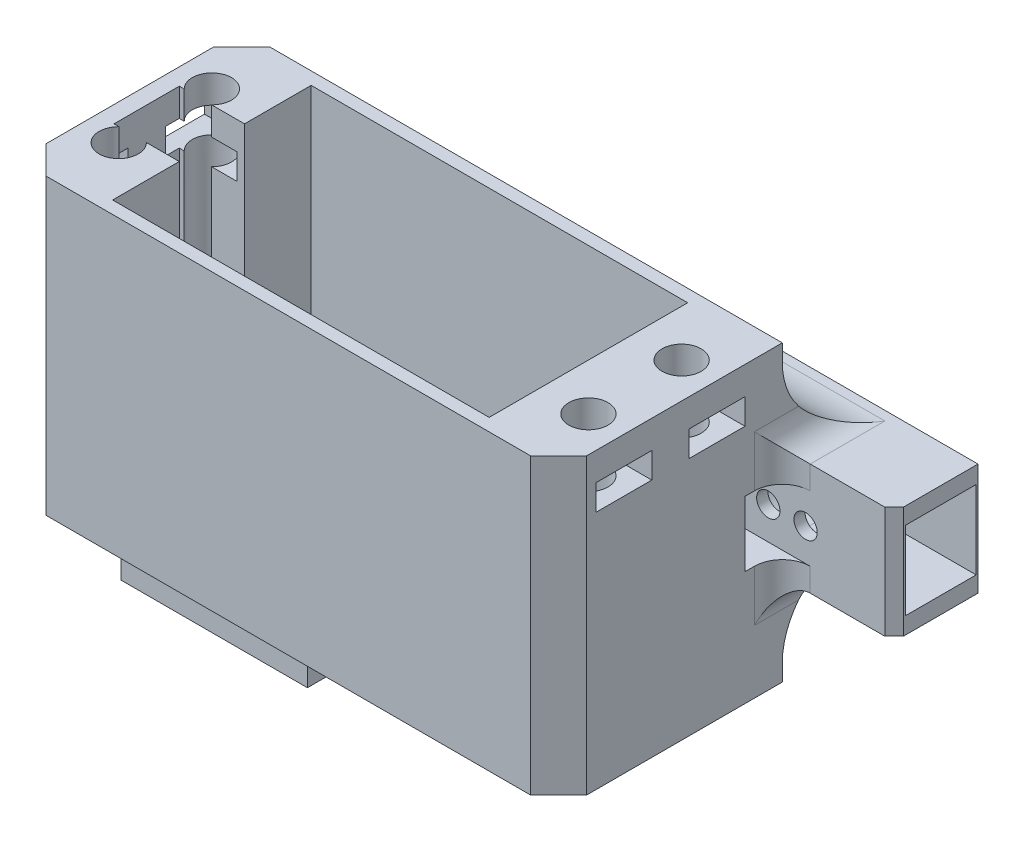
SolidWorks part; units mm, degrees
ref_plane "Front Plane" through (0, 0, 0) normal (0, 0, 1) x (1, 0, 0)
ref_plane "Top Plane" through (0, 0, 0) normal (0, 1, 0) x (1, 0, 0)
ref_plane "Right Plane" through (0, 0, 0) normal (1, 0, 0) x (0, 0, -1)
sketch "Sketch1" plane through (0, 0, 0) normal (0, 1, 0) x (1, 0, 0)
  line L0 (9.75, 1.0273) -> (50.15, 1.0273)
  line L1 (50.15, 1.0273) -> (50.15, -20.2727)
  line L2 (50.15, -20.2727) -> (9.75, -20.2727)
  line L4 (0.95, -21.6227) -> (58.95, -21.6227)
  line L5 (58.95, -21.6227) -> (58.95, 2.3773)
  line L6 (58.95, 2.3773) -> (0.95, 2.3773)
  line L8 (55.15, -4.6227) -> (55.15, -14.6227) construction
  line L9 (0.95, 2.3773) -> (0.95, -21.6227)
  line L10 (9.75, 1.0273) -> (9.75, -20.2727)
  line L11 (29.95, 1.0273) -> (29.95, -20.2727) construction
  circle A0 centre (55.15, -4.6227) radius 2.1
  circle A1 centre (55.15, -14.6227) radius 2.1
  circle A2 centre (4.75, -14.6227) radius 2.1
  circle A3 centre (4.75, -4.6227) radius 2.1
  point P13 (55.15, -9.6227)
  point P14 (50.15, -9.6227)
  point P20 (0.95, -9.6227)
  point P22 (29.95, 2.3773)
  dimension "D1" = 4.2
  dimension "D2" = 10
  dimension "D3" = 24
  dimension "D4" = 40.4
  dimension "D5" = 5
  dimension "D6" = 21.3
  dimension "D7" = 58
extrude "Boss-Extrude1" add sketch "Sketch1" along normal blind 28.35
sketch "Sketch11" plane through (0, 0, 0) normal (0, -1, 0) x (1, 0, 0)
  line L1 (0.95, 21.6227) -> (58.95, 21.6227)
  line L2 (0.95, 21.6227) -> (0.95, -2.3773)
  line L3 (0.95, -2.3773) -> (58.95, -2.3773)
  line L4 (58.95, 21.6227) -> (58.95, -2.3773)
extrude "Boss-Extrude5" add sketch "Sketch11" along normal blind 3.175
sketch "Sketch14" plane through (0, 0, -2.3773) normal (0, 0, -1) x (-1, 0, 0)
  line L7 (-58.95, 28.35) -> (-58.95, -3.175) construction
  line L8 (-46.95, 6.5875) -> (-70.95, 6.5875)
  line L9 (-46.95, 6.5875) -> (-46.95, 18.5875)
  line L10 (-46.95, 18.5875) -> (-70.95, 18.5875)
  line L11 (-70.95, 6.5875) -> (-70.95, 18.5875)
  line L12 (-46.95, 6.5875) -> (-70.95, 18.5875) construction
  line L13 (-46.95, 18.5875) -> (-70.95, 6.5875) construction
  point P0 (-58.95, 12.5875)
  point P5 (-58.95, 12.5875)
  dimension "D1" = 24
  dimension "D2" = 12
  dimension "D3" = 0
extrude "Boss-Extrude7" add sketch "Sketch14" along normal blind 10
ref_plane "Plane1" through (0, 0, -7.3773) normal (0, 0, 1) x (1, 0, 0)
sketch "Sketch16" plane through (0, 0, -7.3773) normal (0, 0, 1) x (1, 0, 0)
  line L0 (70.95, 18.5875) -> (70.95, 6.5875) construction
  line L1 (57.45, 8.3875) -> (70.95, 8.3875)
  line L3 (57.45, 16.7875) -> (70.95, 16.7875)
  line L4 (70.95, 8.3875) -> (70.95, 16.7875)
  line L5 (46.95, 6.5875) -> (46.95, 18.5875) construction
  arc A0 (57.45, 16.7875) -> (57.45, 8.3875) centre (57.45, 12.5875) ccw
  point P9 (46.95, 12.5875)
  point P10 (70.95, 12.5875)
  dimension "D2" = 4.2
  dimension "D1" = 13.5
extrude "Cut-Extrude1" cut sketch "Sketch16" against normal mid plane 7.6
sketch "Sketch18" plane through (0, 0, -12.3773) normal (0, 0, -1) x (-1, 0, 0)
  arc A0 (-60.2, 12.5875) -> (-62.7, 12.5875) centre (-61.45, 12.5875) ccw construction
  arc A1 (-62.7, 12.5875) -> (-60.2, 12.5875) centre (-61.45, 12.5875) ccw construction
  arc A2 (-56.2, 12.5875) -> (-58.7, 12.5875) centre (-57.45, 12.5875) ccw construction
  arc A3 (-58.7, 12.5875) -> (-56.2, 12.5875) centre (-57.45, 12.5875) ccw construction
  arc A4 (-60.2, 12.5875) -> (-62.7, 12.5875) centre (-61.45, 12.5875) ccw
  arc A5 (-62.7, 12.5875) -> (-60.2, 12.5875) centre (-61.45, 12.5875) ccw
  arc A6 (-56.2, 12.5875) -> (-58.7, 12.5875) centre (-57.45, 12.5875) ccw
  arc A7 (-58.7, 12.5875) -> (-56.2, 12.5875) centre (-57.45, 12.5875) ccw
extrude "Cut-Extrude2" cut sketch "Sketch18" against normal up to surface (10 mm away) up to face at (64.95, 12.5875, -2.3773)
fillet "Fillet1" radius 8 3 edges at (52.95, 6.5875, -2.3773) (46.95, 12.5875, -2.3773) (52.95, 18.5875, -2.3773)
chamfer "Chamfer2" distance 3 angle 45 3 edges at (0.95, 12.5875, -2.3773) (0.95, 12.5875, 21.6227) (58.95, 12.5875, 21.6227)
fillet "Fillet2" radius 3 2 edges at (58.95, 6.5875, -6.3773) (58.95, 18.5875, -6.3773)
fillet "Fillet3" radius 3 1 edges at (58.95, 12.5875, -2.3773)
chamfer "Chamfer3" distance 1 angle 45 5 edges at (70.95, 12.5875, -2.3773) (70.95, 12.5875, -12.3773) (58.95, 6.5875, -12.3773) (46.95, 12.5875, -12.3773) (58.95, 18.5875, -12.3773)
ref_plane "Plane2" through (0, 25.35, 0) normal (0, 1, 0) x (1, 0, 0)
sketch "Sketch19" plane through (0, 25.35, 0) normal (0, 1, 0) x (1, 0, 0)
  line L0 (0.95, -0.6227) -> (0.95, -18.6227) construction
  line L1 (0.95, -1.6227) -> (8.95, -1.6227)
  line L2 (0.95, -1.6227) -> (0.95, -7.6227)
  line L3 (0.95, -7.6227) -> (8.95, -7.6227)
  line L4 (8.95, -1.6227) -> (8.95, -7.6227)
  line L5 (-0.5892, -9.6227) -> (60.8708, -9.6227) construction
  line L6 (29.95, -22.0073) -> (29.95, 3.0189) construction
  line L7 (9.75, 1.0273) -> (9.75, -20.2727) construction
  line L8 (50.15, 1.0273) -> (9.75, 1.0273) construction
  line L9 (8.95, -17.6227) -> (8.95, -11.6227)
  line L10 (0.95, -11.6227) -> (8.95, -11.6227)
  line L11 (0.95, -17.6227) -> (0.95, -11.6227)
  line L12 (0.95, -17.6227) -> (8.95, -17.6227)
  line L37 (60.4892, -9.6227) -> (-0.9708, -9.6227) construction
  line L38 (58.95, -17.6227) -> (50.95, -17.6227)
  line L39 (58.95, -17.6227) -> (58.95, -11.6227)
  line L40 (58.95, -11.6227) -> (50.95, -11.6227)
  line L41 (50.95, -17.6227) -> (50.95, -11.6227)
  line L42 (50.95, -1.6227) -> (50.95, -7.6227)
  line L43 (58.95, -7.6227) -> (50.95, -7.6227)
  line L44 (58.95, -1.6227) -> (58.95, -7.6227)
  line L45 (58.95, -1.6227) -> (50.95, -1.6227)
  circle A0 centre (4.75, -4.6227) radius 2.1 construction
  circle A1 centre (4.75, -4.6227) radius 2.1 construction
  circle A2 centre (4.75, -14.6227) radius 2.1 construction
  circle A3 centre (4.75, -4.6227) radius 2.1 construction
  circle A4 centre (4.75, -14.6227) radius 2.1 construction
  circle A5 centre (4.75, -4.6227) radius 2.1 construction
  circle A6 centre (4.75, -14.6227) radius 2.1 construction
  circle A7 centre (4.75, -4.6227) radius 2.1 construction
  circle A8 centre (4.75, -14.6227) radius 2.1 construction
  circle A9 centre (55.15, -14.6227) radius 2.1 construction
  circle A10 centre (55.15, -4.6227) radius 2.1 construction
  circle A11 centre (55.15, -14.6227) radius 2.1 construction
  circle A12 centre (55.15, -4.6227) radius 2.1 construction
  circle A13 centre (55.15, -14.6227) radius 2.1 construction
  circle A14 centre (55.15, -4.6227) radius 2.1 construction
  circle A15 centre (55.15, -14.6227) radius 2.1 construction
  circle A16 centre (55.15, -4.6227) radius 2.1 construction
  point P11 (0.95, -4.6227)
  point P18 (9.75, -9.6227)
  point P21 (29.95, 1.0273)
  point P28 (0.95, -14.6227)
  point P55 (58.95, -14.6227)
  point P56 (58.95, -4.6227)
  dimension "D1" = 6
  dimension "D2" = 8
extrude "Cut-Extrude3" cut sketch "Sketch19" against normal blind 2.75
sketch "Sketch20" plane through (0, 0, 0) normal (0, 1, 0) x (1, 0, 0)
  line L0 (0.95, -0.6227) -> (0.95, -18.6227) construction
  line L1 (0.95, -13.8727) -> (9.75, -13.8727)
  line L2 (0.95, -13.8727) -> (0.95, -5.3727)
  line L3 (0.95, -5.3727) -> (9.75, -5.3727)
  line L4 (9.75, -13.8727) -> (9.75, -5.3727)
  line L5 (9.75, 1.0273) -> (9.75, -20.2727) construction
  point P6 (0.95, -9.6227)
  dimension "D1" = 8.5
extrude "Cut-Extrude4" cut sketch "Sketch20" along normal blind 4
sketch "Sketch21" plane through (0, -3.175, 0) normal (0, -1, 0) x (1, 0, 0)
  line L0 (0.95, 18.6227) -> (0.95, 0.6227) construction
  line L1 (30, -0.3773) -> (10, -0.3773)
  line L2 (30, -0.3773) -> (30, 19.6227)
  line L3 (30, 19.6227) -> (10, 19.6227)
  line L4 (10, -0.3773) -> (10, 19.6227)
  line L5 (30, -0.3773) -> (10, 19.6227) construction
  line L6 (30, 19.6227) -> (10, -0.3773) construction
  point P0 (20, 9.6227)
  point P7 (0.95, 9.6227)
  dimension "D1" = 19.05
  dimension "D2" = 20
  dimension "D3" = 20
extrude "Boss-Extrude8" add sketch "Sketch21" along normal blind 6
sketch "Sketch13" plane through (0, -9.175, 0) normal (0, -1, 0) x (1, 0, 0)
  line L0 (0.95, 18.6227) -> (0.95, 0.6227) construction
  circle A0 centre (20, 9.6227) radius 2.55
  point P2 (0.95, 9.6227)
  dimension "D2" = 5.1
  dimension "D1" = 19.05
extrude "Boss-Extrude6" add sketch "Sketch13" along normal blind 5
fillet "Fillet4" radius 1 4 edges at (20, -3.175, 19.6227) (30, -3.175, 9.6227) (20, -3.175, -0.3773) (10, -3.175, 9.6227)
chamfer "Chamfer4" distance 2 angle 45 4 edges at (20, -9.175, 19.6227) (30, -9.175, 9.6227) (20, -9.175, -0.3773) (10, -9.175, 9.6227)
fillet "Fillet5" radius 1 1 edges at (20, -14.175, 7.0727)
sketch "Sketch22" plane through (0, 28.35, 0) normal (0, 1, 0) x (1, 0, 0)
  line L0 (9.75, 1.0273) -> (9.75, -20.2727) construction
  line L2 (9.75, -6.1227) -> (2.75, -6.1227)
  line L3 (9.75, -6.1227) -> (9.75, -13.1227)
  line L4 (9.75, -13.1227) -> (2.75, -13.1227)
  line L5 (2.75, -6.1227) -> (2.75, -13.1227)
  point P0 (9.75, -9.6227)
  dimension "D1" = 7
  dimension "D2" = 7
extrude "Cut-Extrude5" cut sketch "Sketch22" against normal up to surface (28.35 mm away) up to face at (13.35, 0, 9.6227)
sketch "Sketch23" plane through (0, 0, -12.3773) normal (0, 0, -1) x (-1, 0, 0)
  line L14 (-69.95, 17.5875) -> (-69.95, 7.5875) construction
  line L15 (-64.6254, 16.0875) -> (-52.6254, 16.0875)
  line L16 (-64.6254, 16.0875) -> (-64.6254, 9.0875)
  line L17 (-64.6254, 9.0875) -> (-52.6254, 9.0875)
  line L18 (-52.6254, 16.0875) -> (-52.6254, 9.0875)
  point P4 (-69.95, 12.5875)
  point P5 (-64.6254, 12.5875)
  dimension "D1" = 7
  dimension "D2" = 12
  dimension "D4" = 5.3246
extrude "Cut-Extrude6" cut sketch "Sketch23" against normal blind 4 from surface starting at face at (64.7417, 12.5875, -2.3773)
